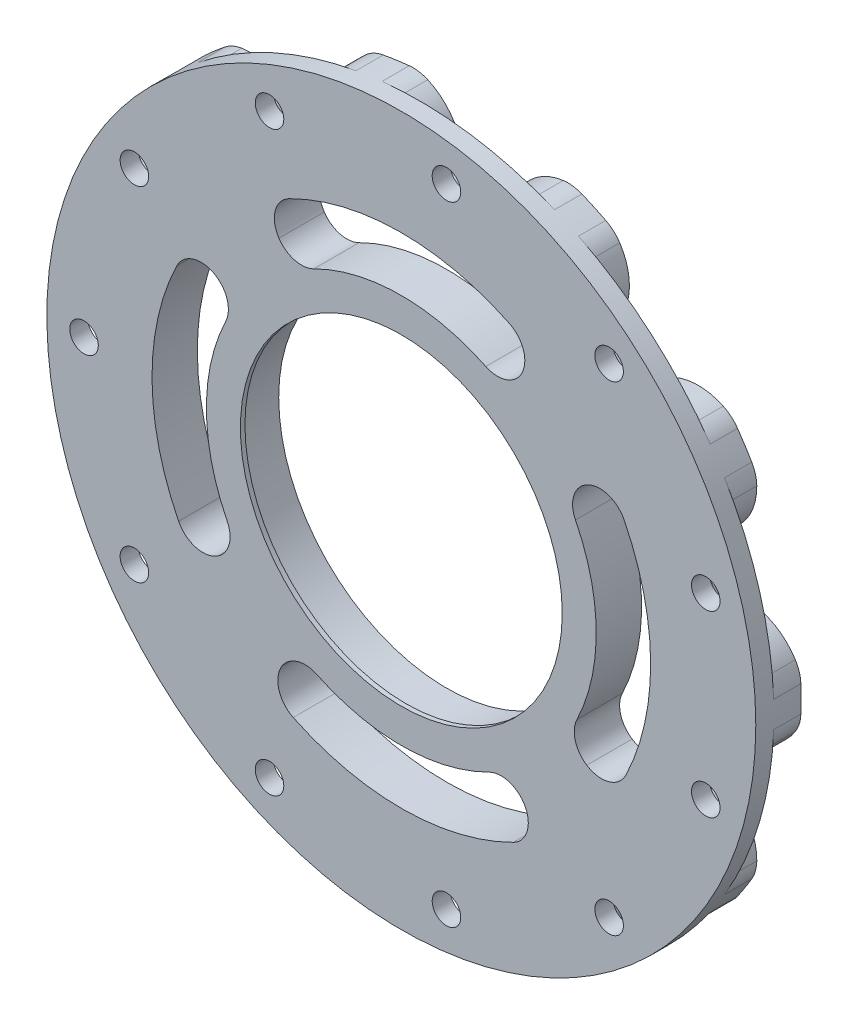
SolidWorks part; units mm, degrees
material "ABS"
ref_plane "Front Plane" through (0, 0, 0) normal (0, 0, 1) x (1, 0, 0)
ref_plane "Top Plane" through (0, 0, 0) normal (0, 1, 0) x (1, 0, 0)
ref_plane "Right Plane" through (0, 0, 0) normal (1, 0, 0) x (0, 0, -1)
ref_plane "Plane1" through (0, 0, 15) normal (0, 0, 1) x (1, 0, 0)
sketch "Sketch1" plane through (0, 0, 15) normal (0, 0, 1) x (1, 0, 0)
  circle A0 centre (0, 0) radius 39.1
  circle A1 centre (0, 0) radius 33 construction
  circle A2 centre (33, 0) radius 2.525
  circle A3 centre (27.7614, -17.8411) radius 2.525
  circle A4 centre (13.7087, -30.0179) radius 2.525
  circle A5 centre (-4.6964, -32.6641) radius 2.525
  circle A6 centre (-21.6104, -24.9397) radius 2.525
  circle A7 centre (-31.6633, -9.2972) radius 2.525
  circle A8 centre (-31.6633, 9.2972) radius 2.525
  circle A9 centre (-21.6104, 24.9397) radius 2.525
  circle A10 centre (-4.6964, 32.6641) radius 2.525
  circle A11 centre (13.7087, 30.0179) radius 2.525
  circle A12 centre (27.7614, 17.8411) radius 2.525
  circle A13 centre (0, 0) radius 16.025
  point P28 (0, 0)
extrude "Boss-Extrude1" add sketch "Sketch1" along normal blind 5
sketch "Sketch2" plane through (0, 0, 15) normal (0, 0, -1) x (-1, 0, 0)
  circle A0 centre (0, 0) radius 18.525
  dimension "D1" = 37.05
extrude "Cut-Extrude1" cut sketch "Sketch2" against normal blind 4.5
sketch "Sketch3" plane through (0, 0, 20) normal (0, 0, 1) x (1, 0, 0)
  circle A1 centre (-4.6964, 32.6641) radius 2.55
  circle A2 centre (13.7087, 30.0179) radius 2.55
  circle A4 centre (27.7614, 17.8411) radius 2.55
  circle A6 centre (33, 0) radius 2.55
  circle A8 centre (27.7614, -17.8411) radius 2.55
  circle A10 centre (13.7087, -30.0179) radius 2.55
  circle A12 centre (-4.6964, -32.6641) radius 2.55
  circle A14 centre (-21.6104, -24.9397) radius 2.55
  circle A16 centre (-31.6633, -9.2972) radius 2.55
  circle A18 centre (-31.6633, 9.2972) radius 2.55
  circle A20 centre (-21.6104, 24.9397) radius 2.55
  point P36 (0, 0)
  dimension "D1" = 5.1
  dimension "D3" = 11
extrude "Boss-Extrude2" add sketch "Sketch3" against normal blind 2
chamfer "Chamfer3" distance 0.5 angle 45 11 edges at (35.525, 0, 15) (30.2864, -17.8411, 15) (16.2337, -30.0179, 15) (-2.1714, -32.6641, 15) (-19.0854, -24.9397, 15) (-29.1383, -9.2972, 15) (-29.1383, 9.2972, 15) (-19.0854, 24.9397, 15) (-2.1714, 32.6641, 15) (16.2337, 30.0179, 15) (30.2864, 17.8411, 15)
sketch "Sketch4" plane through (0, 0, 15) normal (0, 0, -1) x (-1, 0, 0)
  arc A0 (-7.5917, 32.0635) -> (-19.2605, 26.7345) centre (-13.7087, 30.0179) ccw
  circle A1 centre (0, 0) radius 39.1
  arc A2 (10.9483, 31.0779) -> (-1.7492, 32.9035) centre (4.6964, 32.6641) ccw
  arc A3 (26.0123, 20.2253) -> (16.3175, 28.6259) centre (21.6104, 24.9397) ccw
  arc A4 (32.8176, 2.9513) -> (29.2035, 15.2597) centre (31.6633, 9.2972) ccw
  arc A5 (29.2035, -15.2597) -> (32.8176, -2.9513) centre (31.6633, -9.2972) ccw
  arc A6 (16.3175, -28.6259) -> (26.0123, -20.2253) centre (21.6104, -24.9397) ccw
  arc A7 (-1.7492, -32.9035) -> (10.9483, -31.0779) centre (4.6964, -32.6641) ccw
  arc A8 (-19.2605, -26.7345) -> (-7.5917, -32.0635) centre (-13.7087, -30.0179) ccw
  arc A9 (-30.6567, -12.0775) -> (-23.7214, -22.8692) centre (-27.7614, -17.8411) ccw
  arc A10 (-32.3197, 6.414) -> (-32.3197, -6.414) centre (-33, 0) ccw
  arc A11 (-23.7214, 22.8692) -> (-30.6567, 12.0775) centre (-27.7614, 17.8411) ccw
  arc A12 (-32.3197, -6.414) -> (-30.6567, -12.0775) centre (0, 0) ccw
  arc A13 (-30.6567, 12.0775) -> (-32.3197, 6.414) centre (0, 0) ccw
  arc A14 (-19.2605, 26.7345) -> (-23.7214, 22.8692) centre (0, 0) ccw
  arc A15 (-1.7492, 32.9035) -> (-7.5917, 32.0635) centre (0, 0) ccw
  arc A16 (16.3175, 28.6259) -> (10.9483, 31.0779) centre (0, 0) ccw
  arc A17 (29.2035, 15.2597) -> (26.0123, 20.2253) centre (0, 0) ccw
  arc A18 (32.8176, -2.9513) -> (32.8176, 2.9513) centre (0, 0) ccw
  arc A19 (26.0123, -20.2253) -> (29.2035, -15.2597) centre (0, 0) ccw
  arc A20 (10.9483, -31.0779) -> (16.3175, -28.6259) centre (0, 0) ccw
  arc A21 (-7.5917, -32.0635) -> (-1.7492, -32.9035) centre (0, 0) ccw
  arc A22 (-23.7214, -22.8692) -> (-19.2605, -26.7345) centre (0, 0) ccw
  point P28 (0, 0)
  circle M36 centre (0, 0) radius 39.1
  dimension "D1" = 12.9
  dimension "D2" = 78.2
  dimension "D4" = 65.9
  dimension "D3" = 11
extrude "Cut-Extrude2" cut sketch "Sketch4" against normal blind 3 contours A15 A2 A0 M36 | A16 A3 A2 M36 | A17 A4 A3 M36 | A18 A5 A4 M36 | A19 A6 A5 M36 | A20 A7 A6 M36 | A21 A8 A7 M36 | A22 A9 A8 M36 | A12 A10 A9 M36 | A13 A11 A10 M36 | A14 A0 A11 M36 region at (5.1877, 36.0815, 15) region at (23.8713, 27.549, 15) region at (-15.1429, 33.1584, 15) region at (34.9759, 10.2699, 15) region at (-30.6658, 19.7077, 15) region at (34.9759, -10.2699, 15) region at (-36.4525, 0, 15) region at (23.8713, -27.549, 15) region at (5.1877, -36.0815, 15) region at (-30.6658, -19.7077, 15) region at (-15.1429, -33.1584, 15)
fillet "Fillet1" radius 4 22 edges at (-38.0948, -8.809, 16.5) (-36.8099, -13.185, 16.5) (-27.2848, -28.0062, 16.5) (-23.8381, -30.9928, 16.5) (-7.8122, -38.3116, 16.5) (-3.2979, -38.9607, 16.5) (14.1408, -36.4534, 16.5) (18.2894, -34.5588, 16.5) (31.6042, -23.0214, 16.5) (34.0699, -19.1847, 16.5) (39.0334, 2.2804, 16.5) (39.0334, -2.2804, 16.5) (34.0699, 19.1847, 16.5) (31.6042, 23.0214, 16.5) (14.1408, 36.4534, 16.5) (18.2894, 34.5588, 16.5) (-3.2979, 38.9607, 16.5) (-7.8122, 38.3116, 16.5) (-38.0948, 8.809, 16.5) (-36.8099, 13.185, 16.5) (-27.2848, 28.0062, 16.5) (-23.8381, 30.9928, 16.5)
sketch "Sketch5" plane through (0, 0, 20) normal (0, 0, 1) x (1, 0, 0)
  circle A0 centre (0, 0) radius 17.75
  dimension "D1" = 35.5
extrude "Cut-Extrude3" cut sketch "Sketch5" against normal blind 10
chamfer "Chamfer5" [suppressed] distance 0.5 angle 45
sketch "Sketch6" plane through (0, 0, 15) normal (0, 0, -1) x (-1, 0, 0)
  line L0 (0, 0) -> (-27.4458, 18.3229)
  line L1 (0, 0) -> (-27.7614, -17.8411)
  line L2 (0, 0) -> (18.3229, 27.4458)
  line L3 (0, 0) -> (-17.8411, 27.7614)
  line L4 (0, 0) -> (27.4458, -18.3229)
  line L5 (0, 0) -> (27.7614, 17.8411)
  line L6 (0, 0) -> (-18.3229, -27.4458)
  line L7 (0, 0) -> (17.8411, -27.7614)
  line L8 (0, 0) -> (-33, 0) construction
  arc A0 (-18.087, -11.6238) -> (-17.8813, 11.9377) centre (0, 0) cw
  arc A1 (-23.1345, -14.8676) -> (-22.8715, 15.2691) centre (0, 0) cw
  arc A2 (-14.8676, 23.1345) -> (15.2691, 22.8715) centre (0, 0) cw
  arc A3 (-11.6238, 18.087) -> (11.9377, 17.8813) centre (0, 0) cw
  arc A4 (23.1345, 14.8676) -> (22.8715, -15.2691) centre (0, 0) cw
  arc A5 (18.087, 11.6238) -> (17.8813, -11.9377) centre (0, 0) cw
  arc A6 (14.8676, -23.1345) -> (-15.2691, -22.8715) centre (0, 0) cw
  arc A7 (11.6238, -18.087) -> (-11.9377, -17.8813) centre (0, 0) cw
  point P31 (0, 0)
  dimension "D1" = 21.5
  dimension "D2" = 27.5
  dimension "D4" = 33.727
  dimension "D5" = 32.727
  dimension "D3" = 4
extrude "Cut-Extrude4" cut sketch "Sketch6" against normal through all contours A1 L1 A0 L0 | L3 A3 L2 A2 | L5 A5 L4 A4 | L7 A7 L6 A6 | L8 A0 L0 A1 region at (23.2249, 7.0402, 15) region at (23.3052, -6.843, 15) region at (-0.203, 23.2644, 15) region at (-23.2644, -0.203, 15) region at (0.203, -23.2644, 15)
fillet "Fillet2" radius 3 16 edges at (15.2691, -22.8715, 17.5) (11.9377, -17.8813, 17.5) (-11.6238, -18.087, 17.5) (-23.1345, 14.8676, 17.5) (-18.087, 11.6238, 17.5) (-17.8813, -11.9377, 17.5) (-14.8676, -23.1345, 17.5) (-22.8715, -15.2691, 17.5) (18.087, -11.6238, 17.5) (23.1345, -14.8676, 17.5) (22.8715, 15.2691, 17.5) (17.8813, 11.9377, 17.5) (11.6238, 18.087, 17.5) (14.8676, 23.1345, 17.5) (-15.2691, 22.8715, 17.5) (-11.9377, 17.8813, 17.5)
sketch "Sketch7" plane through (0, 0, 20) normal (0, 0, 1) x (1, 0, 0)
  line L0 (0, 0) -> (-35, 0) construction
  circle A0 centre (-35, 0) radius 1.575
  circle A1 centre (-29.4439, 18.9224) radius 1.575
  circle A2 centre (-14.5395, 31.8371) radius 1.575
  circle A3 centre (4.981, 34.6438) radius 1.575
  circle A4 centre (22.9201, 26.4512) radius 1.575
  circle A5 centre (33.5823, 9.8606) radius 1.575
  circle A6 centre (33.5823, -9.8606) radius 1.575
  circle A7 centre (22.9201, -26.4512) radius 1.575
  circle A8 centre (4.981, -34.6438) radius 1.575
  circle A9 centre (-14.5395, -31.8371) radius 1.575
  circle A10 centre (-29.4439, -18.9224) radius 1.575
  point P26 (0, 0)
  dimension "D2" = 3.15
  dimension "D1" = 35
  dimension "D3" = 11
extrude "Cut-Extrude5" cut sketch "Sketch7" against normal through all
equation "\"RingPinShaft\"= 5.05"
equation "\"CenterBearingOut\"=32.05"
equation "\"OutputBearingOut\"=37.05"
equation "\"RingPostIn\"=5.15"
equation "\"CamBearingOut\"=15.1"
equation "\"DiskOutputShaft\"=10.1"
equation "\"CenterShaft\"=25.2"
equation "\"Eccentricity\"=2"
equation "\"CycCamShaft\"=10.05"
equation "\"m3Thru\"=3.15"
equation "\"m3Insert\"=4.2"
equation "\"D1@Sketch2\"=\"OutputBearingOut\""
equation "\"D2@Sketch7\"=\"m3Thru\""
equation "\"MountingHoleDiam\"=35"
equation "\"D1@Sketch7\"=\"MountingHoleDiam\""
